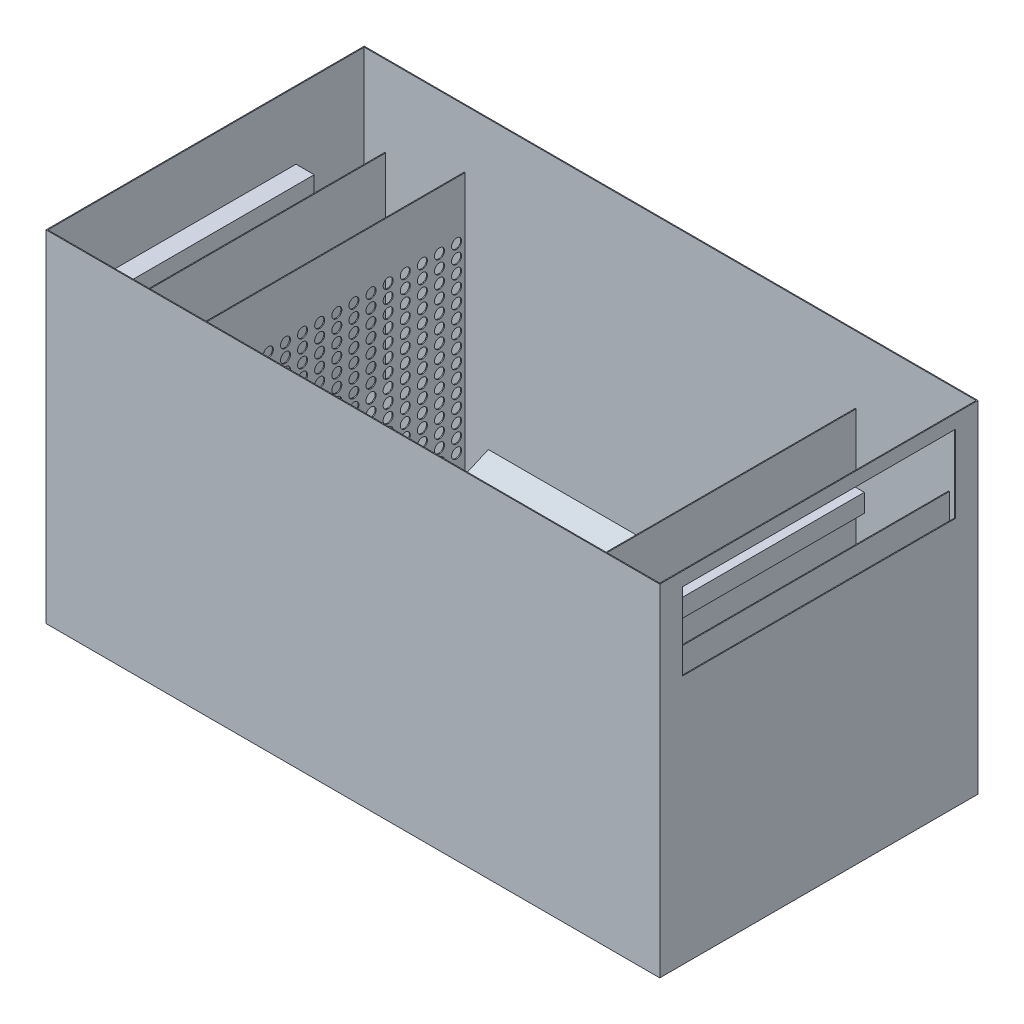
SolidWorks part; units mm, degrees
ref_plane "Спереди" through (0, 0, 0) normal (0, 0, 1) x (1, 0, 0)
ref_plane "Сверху" through (0, 0, 0) normal (0, 1, 0) x (1, 0, 0)
ref_plane "Справа" through (0, 0, 0) normal (1, 0, 0) x (0, 0, -1)
sketch "MASTER_FOOTPRINT" plane through (0, 0, 0) normal (0, 1, 0) x (1, 0, 0)
  line L1 (0, 0) -> (1350, 0)
  line L2 (0, 0) -> (0, 700)
  line L3 (0, 700) -> (1350, 700)
  line L4 (1350, 0) -> (1350, 700)
  dimension "D1" = 1350
  dimension "D2" = 700
extrude "BATH_BASE_PLATE" add sketch "MASTER_FOOTPRINT" along normal blind 750
shell "BATH_SHELL_2MM" thickness 2 removed face at (675, 750, -350)
sketch "Эскиз1" plane through (0, 0, 0) normal (1, 0, 0) x (0, 0, -1)
  circle A0 centre (350, 420) radius 50
extrude "INLET_D100_OPENING" cut sketch "Эскиз1" along normal blind 10
sketch "Эскиз2" plane through (0, 0, 0) normal (1, 0, 0) x (0, 0, -1)
  line L1 (80, 220) -> (620, 220)
  line L2 (80, 220) -> (80, 650)
  line L3 (80, 650) -> (620, 650)
  line L4 (620, 220) -> (620, 650)
extrude "INLET_IMPACT_BAFFLE" add sketch "Эскиз2" along normal blind 2 from offset 125 separate body
sketch "Эскиз3" plane through (0, 0, 0) normal (1, 0, 0) x (0, 0, -1)
  line L1 (30, 2) -> (670, 2)
  line L2 (30, 2) -> (30, 650)
  line L3 (30, 650) -> (670, 650)
  line L4 (670, 2) -> (670, 650)
  circle A0 centre (48.8235, 125) radius 11
  circle A1 centre (48.8235, 153.5) radius 11
  circle A2 centre (48.8235, 182) radius 11
  circle A3 centre (48.8235, 210.5) radius 11
  circle A4 centre (48.8235, 239) radius 11
  circle A5 centre (48.8235, 267.5) radius 11
  circle A6 centre (48.8235, 296) radius 11
  circle A7 centre (48.8235, 324.5) radius 11
  circle A8 centre (48.8235, 353) radius 11
  circle A9 centre (48.8235, 381.5) radius 11
  circle A10 centre (48.8235, 410) radius 11
  circle A11 centre (48.8235, 438.5) radius 11
  circle A12 centre (48.8235, 467) radius 11
  circle A13 centre (48.8235, 495.5) radius 11
  circle A14 centre (48.8235, 524) radius 11
  circle A15 centre (86.4706, 125) radius 11
  circle A16 centre (86.4706, 153.5) radius 11
  circle A17 centre (86.4706, 182) radius 11
  circle A18 centre (86.4706, 210.5) radius 11
  circle A19 centre (86.4706, 239) radius 11
  circle A20 centre (86.4706, 267.5) radius 11
  circle A21 centre (86.4706, 296) radius 11
  circle A22 centre (86.4706, 324.5) radius 11
  circle A23 centre (86.4706, 353) radius 11
  circle A24 centre (86.4706, 381.5) radius 11
  circle A25 centre (86.4706, 410) radius 11
  circle A26 centre (86.4706, 438.5) radius 11
  circle A27 centre (86.4706, 467) radius 11
  circle A28 centre (86.4706, 495.5) radius 11
  circle A29 centre (86.4706, 524) radius 11
  circle A30 centre (124.1176, 125) radius 11
  circle A31 centre (124.1176, 153.5) radius 11
  circle A32 centre (124.1176, 182) radius 11
  circle A33 centre (124.1176, 210.5) radius 11
  circle A34 centre (124.1176, 239) radius 11
  circle A35 centre (124.1176, 267.5) radius 11
  circle A36 centre (124.1176, 296) radius 11
  circle A37 centre (124.1176, 324.5) radius 11
  circle A38 centre (124.1176, 353) radius 11
  circle A39 centre (124.1176, 381.5) radius 11
  circle A40 centre (124.1176, 410) radius 11
  circle A41 centre (124.1176, 438.5) radius 11
  circle A42 centre (124.1176, 467) radius 11
  circle A43 centre (124.1176, 495.5) radius 11
  circle A44 centre (124.1176, 524) radius 11
  circle A45 centre (161.7647, 125) radius 11
  circle A46 centre (161.7647, 153.5) radius 11
  circle A47 centre (161.7647, 182) radius 11
  circle A48 centre (161.7647, 210.5) radius 11
  circle A49 centre (161.7647, 239) radius 11
  circle A50 centre (161.7647, 267.5) radius 11
  circle A51 centre (161.7647, 296) radius 11
  circle A52 centre (161.7647, 324.5) radius 11
  circle A53 centre (161.7647, 353) radius 11
  circle A54 centre (161.7647, 381.5) radius 11
  circle A55 centre (161.7647, 410) radius 11
  circle A56 centre (161.7647, 438.5) radius 11
  circle A57 centre (161.7647, 467) radius 11
  circle A58 centre (161.7647, 495.5) radius 11
  circle A59 centre (161.7647, 524) radius 11
  circle A60 centre (199.4118, 125) radius 11
  circle A61 centre (199.4118, 153.5) radius 11
  circle A62 centre (199.4118, 182) radius 11
  circle A63 centre (199.4118, 210.5) radius 11
  circle A64 centre (199.4118, 239) radius 11
  circle A65 centre (199.4118, 267.5) radius 11
  circle A66 centre (199.4118, 296) radius 11
  circle A67 centre (199.4118, 324.5) radius 11
  circle A68 centre (199.4118, 353) radius 11
  circle A69 centre (199.4118, 381.5) radius 11
  circle A70 centre (199.4118, 410) radius 11
  circle A71 centre (199.4118, 438.5) radius 11
  circle A72 centre (199.4118, 467) radius 11
  circle A73 centre (199.4118, 495.5) radius 11
  circle A74 centre (199.4118, 524) radius 11
  circle A75 centre (237.0588, 125) radius 11
  circle A76 centre (237.0588, 153.5) radius 11
  circle A77 centre (237.0588, 182) radius 11
  circle A78 centre (237.0588, 210.5) radius 11
  circle A79 centre (237.0588, 239) radius 11
  circle A80 centre (237.0588, 267.5) radius 11
  circle A81 centre (237.0588, 296) radius 11
  circle A82 centre (237.0588, 324.5) radius 11
  circle A83 centre (237.0588, 353) radius 11
  circle A84 centre (237.0588, 381.5) radius 11
  circle A85 centre (237.0588, 410) radius 11
  circle A86 centre (237.0588, 438.5) radius 11
  circle A87 centre (237.0588, 467) radius 11
  circle A88 centre (237.0588, 495.5) radius 11
  circle A89 centre (237.0588, 524) radius 11
  circle A90 centre (274.7059, 125) radius 11
  circle A91 centre (274.7059, 153.5) radius 11
  circle A92 centre (274.7059, 182) radius 11
  circle A93 centre (274.7059, 210.5) radius 11
  circle A94 centre (274.7059, 239) radius 11
  circle A95 centre (274.7059, 267.5) radius 11
  circle A96 centre (274.7059, 296) radius 11
  circle A97 centre (274.7059, 324.5) radius 11
  circle A98 centre (274.7059, 353) radius 11
  circle A99 centre (274.7059, 381.5) radius 11
  circle A100 centre (274.7059, 410) radius 11
  circle A101 centre (274.7059, 438.5) radius 11
  circle A102 centre (274.7059, 467) radius 11
  circle A103 centre (274.7059, 495.5) radius 11
  circle A104 centre (274.7059, 524) radius 11
  circle A105 centre (312.3529, 125) radius 11
  circle A106 centre (312.3529, 153.5) radius 11
  circle A107 centre (312.3529, 182) radius 11
  circle A108 centre (312.3529, 210.5) radius 11
  circle A109 centre (312.3529, 239) radius 11
  circle A110 centre (312.3529, 267.5) radius 11
  circle A111 centre (312.3529, 296) radius 11
  circle A112 centre (312.3529, 324.5) radius 11
  circle A113 centre (312.3529, 353) radius 11
  circle A114 centre (312.3529, 381.5) radius 11
  circle A115 centre (312.3529, 410) radius 11
  circle A116 centre (312.3529, 438.5) radius 11
  circle A117 centre (312.3529, 467) radius 11
  circle A118 centre (312.3529, 495.5) radius 11
  circle A119 centre (312.3529, 524) radius 11
  circle A120 centre (350, 125) radius 11
  circle A121 centre (350, 153.5) radius 11
  circle A122 centre (350, 182) radius 11
  circle A123 centre (350, 210.5) radius 11
  circle A124 centre (350, 239) radius 11
  circle A125 centre (350, 267.5) radius 11
  circle A126 centre (350, 296) radius 11
  circle A127 centre (350, 324.5) radius 11
  circle A128 centre (350, 353) radius 11
  circle A129 centre (350, 381.5) radius 11
  circle A130 centre (350, 410) radius 11
  circle A131 centre (350, 438.5) radius 11
  circle A132 centre (350, 467) radius 11
  circle A133 centre (350, 495.5) radius 11
  circle A134 centre (350, 524) radius 11
  circle A135 centre (387.6471, 125) radius 11
  circle A136 centre (387.6471, 153.5) radius 11
  circle A137 centre (387.6471, 182) radius 11
  circle A138 centre (387.6471, 210.5) radius 11
  circle A139 centre (387.6471, 239) radius 11
  circle A140 centre (387.6471, 267.5) radius 11
  circle A141 centre (387.6471, 296) radius 11
  circle A142 centre (387.6471, 324.5) radius 11
  circle A143 centre (387.6471, 353) radius 11
  circle A144 centre (387.6471, 381.5) radius 11
  circle A145 centre (387.6471, 410) radius 11
  circle A146 centre (387.6471, 438.5) radius 11
  circle A147 centre (387.6471, 467) radius 11
  circle A148 centre (387.6471, 495.5) radius 11
  circle A149 centre (387.6471, 524) radius 11
  circle A150 centre (425.2941, 125) radius 11
  circle A151 centre (425.2941, 153.5) radius 11
  circle A152 centre (425.2941, 182) radius 11
  circle A153 centre (425.2941, 210.5) radius 11
  circle A154 centre (425.2941, 239) radius 11
  circle A155 centre (425.2941, 267.5) radius 11
  circle A156 centre (425.2941, 296) radius 11
  circle A157 centre (425.2941, 324.5) radius 11
  circle A158 centre (425.2941, 353) radius 11
  circle A159 centre (425.2941, 381.5) radius 11
  circle A160 centre (425.2941, 410) radius 11
  circle A161 centre (425.2941, 438.5) radius 11
  circle A162 centre (425.2941, 467) radius 11
  circle A163 centre (425.2941, 495.5) radius 11
  circle A164 centre (425.2941, 524) radius 11
  circle A165 centre (462.9412, 125) radius 11
  circle A166 centre (462.9412, 153.5) radius 11
  circle A167 centre (462.9412, 182) radius 11
  circle A168 centre (462.9412, 210.5) radius 11
  circle A169 centre (462.9412, 239) radius 11
  circle A170 centre (462.9412, 267.5) radius 11
  circle A171 centre (462.9412, 296) radius 11
  circle A172 centre (462.9412, 324.5) radius 11
  circle A173 centre (462.9412, 353) radius 11
  circle A174 centre (462.9412, 381.5) radius 11
  circle A175 centre (462.9412, 410) radius 11
  circle A176 centre (462.9412, 438.5) radius 11
  circle A177 centre (462.9412, 467) radius 11
  circle A178 centre (462.9412, 495.5) radius 11
  circle A179 centre (462.9412, 524) radius 11
  circle A180 centre (500.5882, 125) radius 11
  circle A181 centre (500.5882, 153.5) radius 11
  circle A182 centre (500.5882, 182) radius 11
  circle A183 centre (500.5882, 210.5) radius 11
  circle A184 centre (500.5882, 239) radius 11
  circle A185 centre (500.5882, 267.5) radius 11
  circle A186 centre (500.5882, 296) radius 11
  circle A187 centre (500.5882, 324.5) radius 11
  circle A188 centre (500.5882, 353) radius 11
  circle A189 centre (500.5882, 381.5) radius 11
  circle A190 centre (500.5882, 410) radius 11
  circle A191 centre (500.5882, 438.5) radius 11
  circle A192 centre (500.5882, 467) radius 11
  circle A193 centre (500.5882, 495.5) radius 11
  circle A194 centre (500.5882, 524) radius 11
  circle A195 centre (538.2353, 125) radius 11
  circle A196 centre (538.2353, 153.5) radius 11
  circle A197 centre (538.2353, 182) radius 11
  circle A198 centre (538.2353, 210.5) radius 11
  circle A199 centre (538.2353, 239) radius 11
  circle A200 centre (538.2353, 267.5) radius 11
  circle A201 centre (538.2353, 296) radius 11
  circle A202 centre (538.2353, 324.5) radius 11
  circle A203 centre (538.2353, 353) radius 11
  circle A204 centre (538.2353, 381.5) radius 11
  circle A205 centre (538.2353, 410) radius 11
  circle A206 centre (538.2353, 438.5) radius 11
  circle A207 centre (538.2353, 467) radius 11
  circle A208 centre (538.2353, 495.5) radius 11
  circle A209 centre (538.2353, 524) radius 11
  circle A210 centre (575.8824, 125) radius 11
  circle A211 centre (575.8824, 153.5) radius 11
  circle A212 centre (575.8824, 182) radius 11
  circle A213 centre (575.8824, 210.5) radius 11
  circle A214 centre (575.8824, 239) radius 11
  circle A215 centre (575.8824, 267.5) radius 11
  circle A216 centre (575.8824, 296) radius 11
  circle A217 centre (575.8824, 324.5) radius 11
  circle A218 centre (575.8824, 353) radius 11
  circle A219 centre (575.8824, 381.5) radius 11
  circle A220 centre (575.8824, 410) radius 11
  circle A221 centre (575.8824, 438.5) radius 11
  circle A222 centre (575.8824, 467) radius 11
  circle A223 centre (575.8824, 495.5) radius 11
  circle A224 centre (575.8824, 524) radius 11
  circle A225 centre (613.5294, 125) radius 11
  circle A226 centre (613.5294, 153.5) radius 11
  circle A227 centre (613.5294, 182) radius 11
  circle A228 centre (613.5294, 210.5) radius 11
  circle A229 centre (613.5294, 239) radius 11
  circle A230 centre (613.5294, 267.5) radius 11
  circle A231 centre (613.5294, 296) radius 11
  circle A232 centre (613.5294, 324.5) radius 11
  circle A233 centre (613.5294, 353) radius 11
  circle A234 centre (613.5294, 381.5) radius 11
  circle A235 centre (613.5294, 410) radius 11
  circle A236 centre (613.5294, 438.5) radius 11
  circle A237 centre (613.5294, 467) radius 11
  circle A238 centre (613.5294, 495.5) radius 11
  circle A239 centre (613.5294, 524) radius 11
  circle A240 centre (651.1765, 125) radius 11
  circle A241 centre (651.1765, 153.5) radius 11
  circle A242 centre (651.1765, 182) radius 11
  circle A243 centre (651.1765, 210.5) radius 11
  circle A244 centre (651.1765, 239) radius 11
  circle A245 centre (651.1765, 267.5) radius 11
  circle A246 centre (651.1765, 296) radius 11
  circle A247 centre (651.1765, 324.5) radius 11
  circle A248 centre (651.1765, 353) radius 11
  circle A249 centre (651.1765, 381.5) radius 11
  circle A250 centre (651.1765, 410) radius 11
  circle A251 centre (651.1765, 438.5) radius 11
  circle A252 centre (651.1765, 467) radius 11
  circle A253 centre (651.1765, 495.5) radius 11
  circle A254 centre (651.1765, 524) radius 11
extrude "DISTRIBUTOR_D22" add sketch "Эскиз3" along normal blind 2 from offset 250 separate body
sketch "Эскиз4" plane through (0, 0, 0) normal (1, 0, 0) x (0, 0, -1)
  line L1 (50, 320) -> (650, 320)
  line L2 (50, 320) -> (50, 650)
  line L3 (50, 650) -> (650, 650)
  line L4 (650, 320) -> (650, 650)
extrude "OUTLET_SUBMERGED_BAFFLE" add sketch "Эскиз4" along normal blind 2 from offset 1130 separate body
sketch "Эскиз5" plane through (0, 0, 0) normal (1, 0, 0) x (0, 0, -1)
  line L1 (5, 2) -> (695, 2)
  line L2 (5, 2) -> (5, 550)
  line L3 (5, 550) -> (695, 550)
  line L4 (695, 2) -> (695, 550)
extrude "OVERFLOW_WEIR_Z550" add sketch "Эскиз5" along normal blind 2 from offset 1290 separate body
sketch "Эскиз6" plane through (0, 0, 0) normal (1, 0, 0) x (0, 0, -1)
  line L1 (50, 550) -> (650, 550)
  line L2 (50, 550) -> (50, 720)
  line L3 (50, 720) -> (650, 720)
  line L4 (650, 550) -> (650, 720)
extrude "OUTLET_WEIR_SLOT_W600" cut sketch "Эскиз6" along normal blind 10 from offset 1345
sketch "Эскиз7" plane through (0, 0, 0) normal (1, 0, 0) x (0, 0, -1)
  line L0 (2, -1) -> (2, 120)
  line L1 (2, 120) -> (280, -1)
  line L2 (280, -1) -> (2, -1)
  line L3 (698, -1) -> (698, 120)
  line L4 (698, 120) -> (420, -1)
  line L5 (420, -1) -> (698, -1)
extrude "SLOPED_SEDIMENT_FLOOR" add sketch "Эскиз7" along normal blind 825 from offset 275
sketch3d "SCREW_AXIS_30DEG_REFERENCE"
  line L0 (400, 70, -350) -> (1450, 676.2178, -350)
sketch "Эскиз8" plane through (0, 0, 0) normal (0, 0, 1) x (1, 0, 0)
  line L1 (50, 50) -> (90, 50)
  line L2 (50, 50) -> (50, 90)
  line L3 (50, 90) -> (90, 90)
  line L4 (90, 50) -> (90, 90)
  line L6 (50, 610) -> (90, 610)
  line L7 (50, 610) -> (50, 650)
  line L8 (50, 650) -> (90, 650)
  line L9 (90, 610) -> (90, 650)
  line L11 (1260, 50) -> (1300, 50)
  line L12 (1260, 50) -> (1260, 90)
  line L13 (1260, 90) -> (1300, 90)
  line L14 (1300, 50) -> (1300, 90)
  line L16 (1260, 610) -> (1300, 610)
  line L17 (1260, 610) -> (1260, 650)
  line L18 (1260, 650) -> (1300, 650)
  line L19 (1300, 610) -> (1300, 650)
extrude "FRAME_FOUR_LEGS_40X40" add sketch "Эскиз8" against normal blind 500 separate body
equation "\"AI_Q_Peak\"= 0.006"
equation "\"AI_B_Bath\"= 700"
equation "\"AI_L_Settle\"= 900"
equation "\"AI_L_Inlet\"= 250"
equation "\"AI_L_Outlet\"= 200"
equation "\"AI_L_Bath\"= 1350"
equation "\"AI_H_Water\"= 550"
equation "\"AI_H_Freeboard\"= 200"
equation "\"AI_H_Bath\"= 750"
equation "\"AI_Shell_Thickness\"= 2"
equation "\"AI_Inlet_DN\"= 100"
equation "\"AI_Weir_Width\"= 600"
equation "\"AI_Inlet_Baffle_Offset\"= 125"
equation "\"AI_Distributor_Open_Area\"= 0.28"
equation "\"AI_Distributor_Hole_Dia\"= 22"
equation "\"AI_Distributor_Blind_Zone\"= 110"
equation "\"AI_Outlet_Baffle_Depth\"= 250"
equation "\"AI_Screw_Diameter\"= 100"
equation "\"AI_Screw_Pitch\"= 100"
equation "\"AI_Screw_Angle\"= 30"
equation "\"AI_Screw_Rpm\"= 15"
equation "\"AI_Screw_Clearance\"= 5"
equation "\"AI_Liner_Thickness\"= 5"
equation "\"AI_Discharge_Height\"= 650"
equation "\"AI_Frame_Height\"= 500"
equation "\"D1@MASTER_FOOTPRINT\" = \"AI_L_Bath\""
equation "\"D2@MASTER_FOOTPRINT\" = \"AI_B_Bath\""
equation "\"D1@BATH_BASE_PLATE\" = \"AI_H_Bath\""
